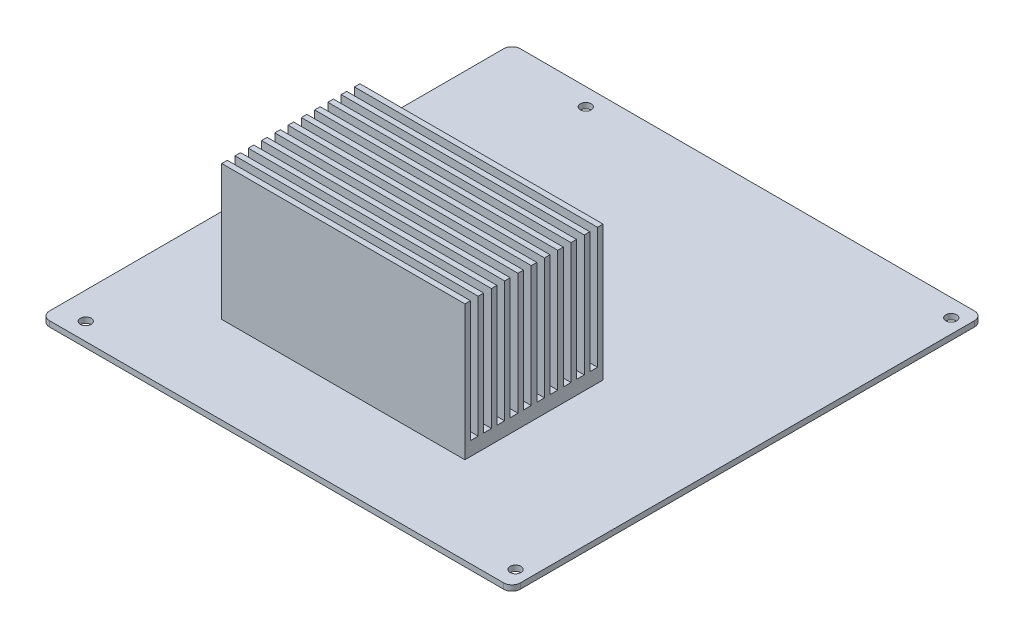
SolidWorks part; units mm, degrees
ref_plane "Front" through (0, 0, 0) normal (0, 0, 1) x (1, 0, 0)
ref_plane "Top" through (0, 0, 0) normal (0, 1, 0) x (1, 0, 0)
ref_plane "Right" through (0, 0, 0) normal (1, 0, 0) x (0, 0, -1)
sketch "Sketch1" plane through (0, 0, 0) normal (0, 1, 0) x (1, 0, 0)
  line L1 (85.09, 85.09) -> (-85.09, 85.09)
  line L2 (85.09, 85.09) -> (85.09, -85.09)
  line L3 (85.09, -85.09) -> (-85.09, -85.09)
  line L4 (-85.09, 85.09) -> (-85.09, -85.09)
  line L5 (85.09, 85.09) -> (-85.09, -85.09) construction
  line L6 (85.09, -85.09) -> (-85.09, 85.09) construction
  point P0 (0, 0)
  dimension "D1" = 170.18
  dimension "D2" = 170.18
extrude "Boss-Extrude1" add sketch "Sketch1" along normal blind 2
sketch "Sketch2" plane through (0, 2, 0) normal (0, 1, 0) x (1, 0, 0)
  line L1 (-51.3234, -3.6387) -> (36.5538, -3.6387)
  line L2 (-51.3234, -3.6387) -> (-51.3234, -53.5762)
  line L3 (-51.3234, -53.5762) -> (36.5538, -53.5762)
  line L4 (36.5538, -3.6387) -> (36.5538, -53.5762)
  line L5 (-51.3234, -3.6387) -> (36.5538, -53.5762) construction
  line L6 (-51.3234, -53.5762) -> (36.5538, -3.6387) construction
  point P0 (-7.3848, -28.6074)
extrude "Boss-Extrude2" add sketch "Sketch2" along normal blind 48.8
fillet "Fillet1" radius 3 4 edges at (-85.09, 1, -85.09) (85.09, 1, -85.09) (85.09, 1, 85.09) (-85.09, 1, 85.09)
hole_wizard "Ø3.9 (3.9) Diameter Hole1" positions "Sketch3" profile "Sketch4" hole size "Ø3.9" standard "ANSI Metric"
sketch "Sketch3" plane through (0, 2, 0) normal (0, 1, 0) x (1, 0, 0)
  line L0 (-82.09, -85.09) -> (82.09, -85.09) construction
  line L1 (85.09, -82.09) -> (85.09, 82.09) construction
  line L3 (-52.07, 78.74) -> (80.01, 78.74) construction
  point P0 (-75.29, -78.74)
  point P2 (80.01, -78.74)
  point P4 (80.01, 78.74)
  point P6 (-52.07, 78.74)
  dimension "D1" = 6.35
  dimension "D2" = 6.35
  dimension "D3" = 5.08
  dimension "D4" = 5.08
  dimension "D5" = 157.48
  dimension "D6" = 132.08
  dimension "D7" = 155.3
sketch "Sketch4" plane through (-75.29, 2, 78.74) normal (1, 0, 0) x (0, 0, 1)
  line L0 (0, 0) -> (0, 19.9217)
  line L1 (0, 19.9217) -> (1.95, 18.75)
  line L2 (1.95, 18.75) -> (1.95, 0)
  line L5 (1.95, 0) -> (0, 0)
  line L10 (0, 19.9217) -> (-1.95, 18.75) construction
  line L11 (0, -6.35) -> (0, 107.95) construction
  dimension "Hole Dia." = 3.9
  dimension "Hole Depth" = 18.75
  dimension "Drill Angle" = 118
sketch "Sketch5" plane through (0, 2, 0) normal (0, 1, 0) x (1, 0, 0)
  line L1 (55.5339, -83.6636) -> (59.9742, -83.6636)
  line L2 (55.5339, -83.6636) -> (55.5339, -75.8548)
  line L3 (55.5339, -75.8548) -> (59.9742, -75.8548)
  line L4 (59.9742, -83.6636) -> (59.9742, -75.8548)
  line L5 (55.5339, -83.6636) -> (59.9742, -75.8548) construction
  line L6 (55.5339, -75.8548) -> (59.9742, -83.6636) construction
  point P0 (57.754, -79.7592)
extrude "Boss-Extrude3" [suppressed] add sketch "Sketch5" along normal blind 50
sketch "Sketch6" plane through (-51.3234, 0, 0) normal (-1, 0, 0) x (0, 0, 1)
  line L0 (3.6387, 50.8) -> (53.5762, 50.8) construction
  line L1 (5.6387, 7) -> (8.4324, 7)
  line L2 (5.6387, 7) -> (5.6387, 50.8)
  line L3 (5.6387, 50.8) -> (8.4324, 50.8)
  line L4 (8.4324, 7) -> (8.4324, 50.8)
  line L5 (5.6387, 7) -> (8.4324, 50.8) construction
  line L6 (5.6387, 50.8) -> (8.4324, 7) construction
  line L7 (3.6387, 50.8) -> (3.6387, 2) construction
  line L8 (53.5762, 50.8) -> (53.5762, 2) construction
  line L9 (13.2262, 7) -> (10.4324, 7)
  line L10 (13.2262, 7) -> (13.2262, 50.8)
  line L11 (13.2262, 50.8) -> (10.4324, 50.8)
  line L12 (10.4324, 7) -> (10.4324, 50.8)
  line L13 (13.2262, 7) -> (10.4324, 50.8) construction
  line L14 (13.2262, 50.8) -> (10.4324, 7) construction
  line L15 (18.0199, 7) -> (15.2262, 7)
  line L16 (18.0199, 7) -> (18.0199, 50.8)
  line L17 (18.0199, 50.8) -> (15.2262, 50.8)
  line L18 (15.2262, 7) -> (15.2262, 50.8)
  line L19 (18.0199, 7) -> (15.2262, 50.8) construction
  line L20 (18.0199, 50.8) -> (15.2262, 7) construction
  line L21 (20.0199, 7) -> (22.8137, 7)
  line L22 (20.0199, 7) -> (20.0199, 50.8)
  line L23 (20.0199, 50.8) -> (22.8137, 50.8)
  line L24 (22.8137, 7) -> (22.8137, 50.8)
  line L25 (20.0199, 7) -> (22.8137, 50.8) construction
  line L26 (20.0199, 50.8) -> (22.8137, 7) construction
  line L27 (24.8137, 7) -> (27.6074, 7)
  line L28 (24.8137, 7) -> (24.8137, 50.8)
  line L29 (24.8137, 50.8) -> (27.6074, 50.8)
  line L30 (27.6074, 7) -> (27.6074, 50.8)
  line L31 (24.8137, 7) -> (27.6074, 50.8) construction
  line L32 (24.8137, 50.8) -> (27.6074, 7) construction
  line L33 (32.4012, 7) -> (29.6074, 7)
  line L34 (32.4012, 7) -> (32.4012, 50.8)
  line L35 (32.4012, 50.8) -> (29.6074, 50.8)
  line L36 (29.6074, 7) -> (29.6074, 50.8)
  line L37 (32.4012, 7) -> (29.6074, 50.8) construction
  line L38 (32.4012, 50.8) -> (29.6074, 7) construction
  line L39 (37.1949, 7) -> (34.4012, 7)
  line L40 (37.1949, 7) -> (37.1949, 50.8)
  line L41 (37.1949, 50.8) -> (34.4012, 50.8)
  line L42 (34.4012, 7) -> (34.4012, 50.8)
  line L43 (37.1949, 7) -> (34.4012, 50.8) construction
  line L44 (37.1949, 50.8) -> (34.4012, 7) construction
  line L45 (41.9887, 7) -> (39.1949, 7)
  line L46 (41.9887, 7) -> (41.9887, 50.8)
  line L47 (41.9887, 50.8) -> (39.1949, 50.8)
  line L48 (39.1949, 7) -> (39.1949, 50.8)
  line L49 (41.9887, 7) -> (39.1949, 50.8) construction
  line L50 (41.9887, 50.8) -> (39.1949, 7) construction
  line L51 (43.9887, 7) -> (46.7824, 7)
  line L52 (43.9887, 7) -> (43.9887, 50.8)
  line L53 (43.9887, 50.8) -> (46.7824, 50.8)
  line L54 (46.7824, 7) -> (46.7824, 50.8)
  line L55 (43.9887, 7) -> (46.7824, 50.8) construction
  line L56 (43.9887, 50.8) -> (46.7824, 7) construction
  line L57 (48.7824, 7) -> (51.5762, 7)
  line L58 (48.7824, 7) -> (48.7824, 50.8)
  line L59 (48.7824, 50.8) -> (51.5762, 50.8)
  line L60 (51.5762, 7) -> (51.5762, 50.8)
  line L61 (48.7824, 7) -> (51.5762, 50.8) construction
  line L62 (48.7824, 50.8) -> (51.5762, 7) construction
  line L63 (3.6387, 2) -> (53.5762, 2) construction
  point P0 (7.0355, 28.9)
  point P7 (16.623, 28.9)
  point P10 (11.8293, 28.9)
  point P19 (21.4168, 28.9)
  point P24 (26.2105, 28.9)
  point P29 (35.798, 28.9)
  point P34 (40.5918, 28.9)
  point P35 (31.0043, 28.9)
  point P44 (50.1793, 28.9)
  point P45 (45.3855, 28.9)
  point P56 (46.2998, 50.8)
  point P57 (51.5762, 13.3176)
  point P58 (51.5762, 5.5454)
  dimension "D1" = 2
  dimension "D2" = 2
  dimension "D3" = 2
  dimension "D4" = 2
  dimension "D5" = 2
  dimension "D6" = 2
  dimension "D7" = 2
  dimension "D8" = 2
  dimension "D9" = 2
  dimension "D10" = 2
  dimension "D11" = 2
  dimension "D12" = 5
extrude "Cut-Extrude1" cut sketch "Sketch6" against normal through all
